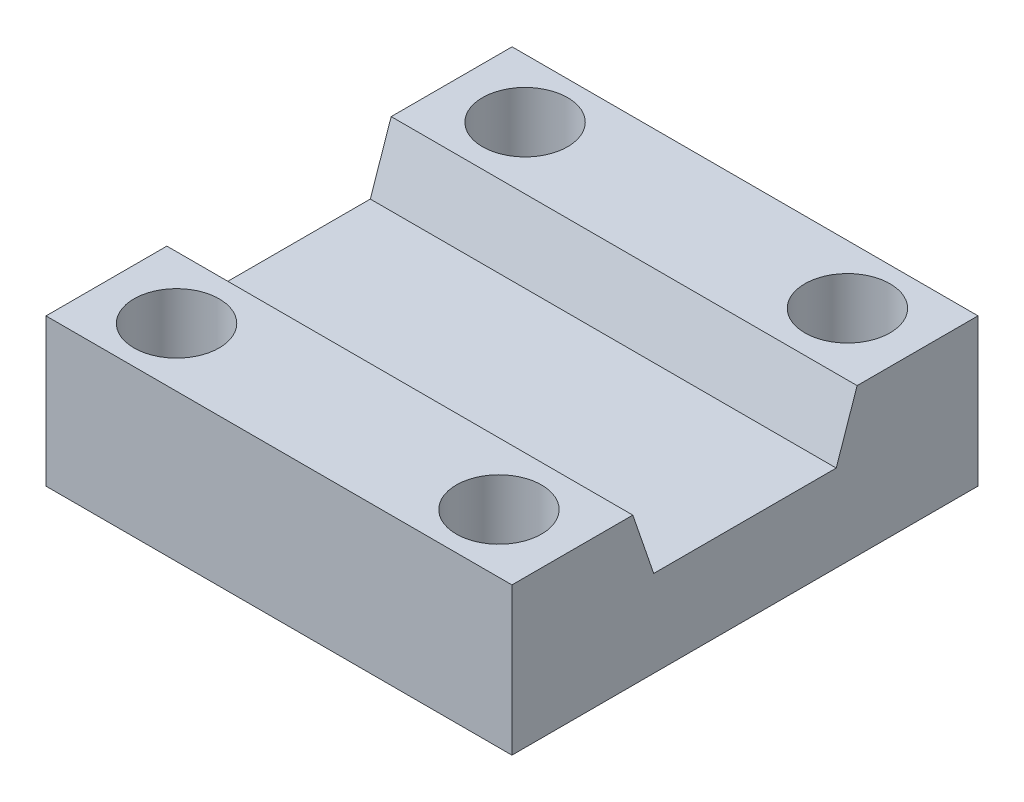
SolidWorks part; units mm, degrees
ref_plane "Front Plane" through (0, 0, 0) normal (0, 0, 1) x (1, 0, 0)
ref_plane "Top Plane" through (0, 0, 0) normal (0, 1, 0) x (1, 0, 0)
ref_plane "Right Plane" through (0, 0, 0) normal (1, 0, 0) x (0, 0, -1)
sketch "Sketch1" plane through (0, 0, 0) normal (0, 1, 0) x (1, 0, 0)
  line L6 (-19.145, 19.15) -> (19.145, 19.15)
  line L7 (-19.145, 19.15) -> (-19.145, -19.15)
  line L8 (-19.145, -19.15) -> (19.145, -19.15)
  line L9 (19.145, 19.15) -> (19.145, -19.15)
  line L10 (-19.145, 19.15) -> (19.145, -19.15) construction
  line L11 (-19.145, -19.15) -> (19.145, 19.15) construction
  point P11 (0, 0)
  dimension "D4" = 38.29
  dimension "D5" = 38.3
extrude "Boss-Extrude1" add sketch "Sketch1" along normal blind 12.12
sketch "Sketch2" plane through (19.145, 0, 0) normal (1, 0, 0) x (0, 0, -1)
  line L0 (-9.2164, 12.12) -> (-7.5, 7.11)
  line L1 (-19.15, 12.12) -> (19.15, 12.12) construction
  line L2 (-7.5, 7.11) -> (7.5, 7.11)
  line L3 (0, 7.11) -> (0, 0) construction
  line L4 (-9.2164, 12.12) -> (9.2164, 12.12)
  line L5 (9.2164, 12.12) -> (7.5, 7.11)
  line L6 (-19.15, 0) -> (19.15, 0) construction
  point P10 (0, 12.12)
  point P12 (9.2164, 12.12)
  dimension "D1" = 7.11
  dimension "D3" = 15
extrude "Cut-Extrude1" cut sketch "Sketch2" against normal through all
hole_wizard "M8x1.0 Tapped Hole2" positions "Sketch6" profile "Sketch7" tap size "M8x1.0" standard "ANSI Metric" end condition through all
sketch "Sketch6" plane through (0, 12.12, 0) normal (0, 1, 0) x (1, 0, 0)
  point P0 (-13.2461, 14.3193)
sketch "Sketch7" plane through (-13.2461, 12.12, -14.3193) normal (1, 0, 0) x (0, 0, 1)
  line L0 (0, 0) -> (0, 12.12)
  line L1 (0, 12.12) -> (3.5, 12.12)
  line L2 (3.5, 12.12) -> (3.5, 0)
  line L5 (3.5, 0) -> (0, 0)
  line L11 (0, -6.35) -> (0, 107.95) construction
  dimension "Thru Tap Drill Dia." = 7
  dimension "Thru Tap Drill Depth" = 12.12
cosmetic thread "Hole Thread5" parameters "D2"=8
mirror "Mirror1" about plane through (0, 0, 0) normal (0, 0, 1) of "M8x1.0 Tapped Hole2" second plane through (0, 0, 0) second plane normal (1, 0, 0)
cosmetic thread "Hole Thread6" parameters "D2"=8
cosmetic thread "Hole Thread7" parameters "D2"=8
cosmetic thread "Hole Thread8" parameters "D2"=8
